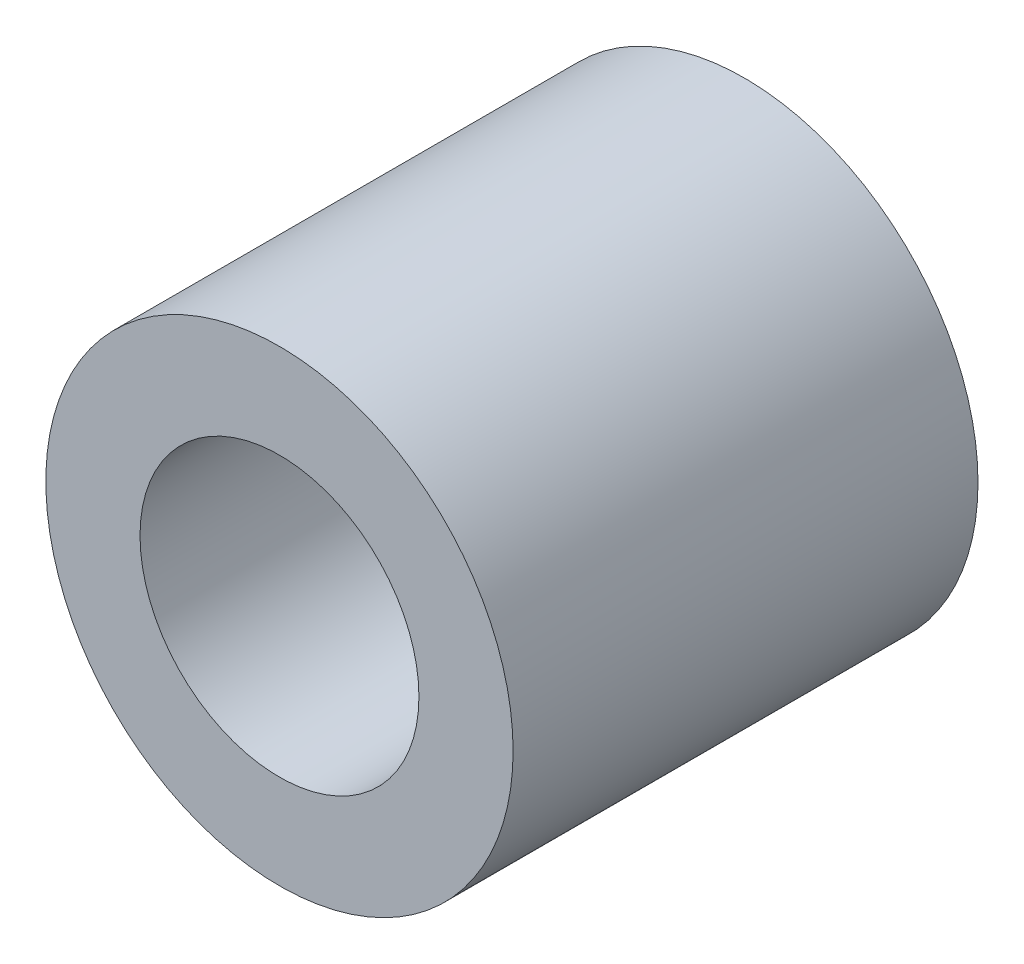
SolidWorks part; units mm, degrees
ref_plane "Front Plane" through (0, 0, 0) normal (0, 0, 1) x (1, 0, 0)
ref_plane "Top Plane" through (0, 0, 0) normal (0, 1, 0) x (1, 0, 0)
ref_plane "Right Plane" through (0, 0, 0) normal (1, 0, 0) x (0, 0, -1)
sketch "Sketch1" plane through (0, 0, 0) normal (0, 0, 1) x (1, 0, 0)
  circle A0 centre (0, 0) radius 5.0255 construction
  circle A1 centre (0, 0) radius 3 construction
  dimension "ID" = 6
  dimension "OD" = 10.051
sketch "Sketch2" plane through (0, 0, 0) normal (1, 0, 0) x (0, 0, -1)
  line L0 (-5, 0) -> (5, 0) construction
  dimension "Length" = 10
sketch "Sketch3" plane through (0, 0, 0) normal (0, 0, 1) x (1, 0, 0)
  circle A0 centre (0, 0) radius 3 construction
  circle A1 centre (0, 0) radius 5.0255 construction
  circle A2 centre (0, 0) radius 3
  circle A3 centre (0, 0) radius 5.0255
extrude "Boss-Extrude1" add sketch "Sketch3" along normal up to vertex (-5 mm away) and the other way up to vertex (-5 mm away) up to point (0, 0, -5) other way up to point (0, 0, 5)
ref_axis "Center Axis 1" through (0, 0, 1.65) along (0, 0, -1)
